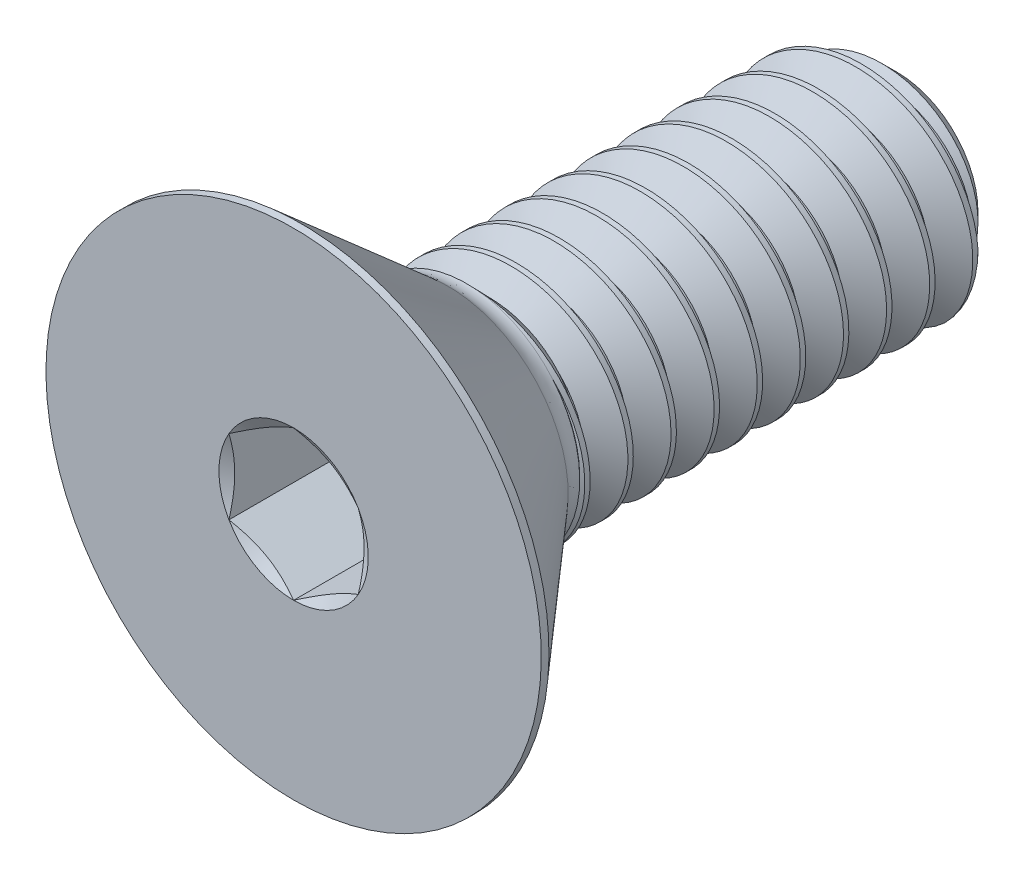
SolidWorks part; units mm, degrees
material "Alloy Steel"
ref_plane "Front" through (0, 0, 0) normal (0, 0, 1) x (1, 0, 0)
ref_plane "Top" through (0, 0, 0) normal (0, 1, 0) x (1, 0, 0)
ref_plane "Right" through (0, 0, 0) normal (1, 0, 0) x (0, 0, -1)
sketch "Sketch1" plane through (0, 0, 0) normal (1, 0, 0) x (0, 0, -1)
  line L0 (0, 4.5593) -> (0.1422, 4.5593) construction
  line L1 (0.1422, 4.5593) -> (2.8448, 2.21) construction
  line L2 (0, 2.0828) -> (11.1125, 2.0828)
  line L3 (11.1125, 2.0828) -> (11.1125, 0)
  line L4 (11.1125, 0) -> (0, 0)
  line L5 (0, 0) -> (0, 4.5593) construction
  line L6 (0, 4.5593) -> (0, -4.5593) construction
  line L7 (11.1125, 2.0828) -> (11.1125, -2.0828) construction
  line L8 (0, -4.5593) -> (0.1422, -4.5593) construction
  line L9 (0.1422, -4.5593) -> (2.8448, -2.21) construction
  line L11 (0, 2.0828) -> (0, 0)
  line L12 (3.185, 2.0828) -> (3.185, 0) construction
  line L13 (-14.2875, 0) -> (-14.2875, 2.0828) construction
  arc A1 (2.8448, 2.21) -> (3.185, 2.0828) centre (3.185, 2.6014) ccw construction
  dimension "D1" = 0.1422
  dimension "Head Ht" = 2.8448
  dimension "Head Dia" = 9.1186
  dimension "Dia" = 4.1656
  dimension "Lg" = 11.1125
  dimension "Head Angle" = 82
  dimension "Min Thread" = 25.4
revolve "Revolve1" add sketch "Sketch1" angle 360 mid plane about L4
sketch "Sketch3" plane through (0, 0, -11.1125) normal (0, 0, -1) x (-1, 0, 0)
  circle A0 centre (0, 0) radius 2.0828
curve "Helix/Spiral1" pitch 0.7937 height 11.1125 radius 2.0828 centre (0, 0, -11.1125) axis (0, 0, 1) start towards (0, 1, 0)
sketch "Sketch2" plane through (0, 0, 0) normal (1, 0, 0) x (0, 0, -1)
  line L0 (11.1125, 2.0828) -> (11.807, 2.0828)
  line L1 (11.807, 2.0828) -> (11.5094, 1.5672)
  line L2 (11.5094, 1.5672) -> (11.4102, 1.5672)
  line L3 (11.4102, 1.5672) -> (11.1125, 2.0828)
  line L4 (11.2613, 1.825) -> (11.6582, 1.825) construction
  dimension "D1" = 60
  dimension "D2" = 0.0992
  dimension "D3" = 0.3969
ref_plane "Plane2" through (0, 0, 14.2875) normal (0, 0, 1) x (1, 0, 0)
chamfer "Chamfer1" distance 0.5953 angle 45 1 edges at (-2.0828, 0, -11.1125)
sweep "Cut-Sweep1" cut profiles "Sketch2" path "Helix/Spiral1"
sketch "Sketch7" plane through (0, 0, 0) normal (1, 0, 0) x (0, 0, -1)
  line L0 (0, 4.5593) -> (0.1422, 4.5593) construction
  line L1 (0.1422, 4.5593) -> (2.8448, 2.21) construction
  line L2 (0, 4.5593) -> (0.1422, 4.5593)
  line L3 (0.1422, 4.5593) -> (2.8448, 2.21)
  line L4 (3.185, 2.0828) -> (3.185, 0) construction
  line L5 (3.185, 2.0828) -> (3.185, 0)
  line L7 (0, 0) -> (0, 4.5593) construction
  line L8 (0, 0) -> (0, 4.5593)
  line L9 (0, 0) -> (3.185, 0)
  line L10 (5.7417, 0) -> (-5.7417, 0) construction
  arc A0 (2.8448, 2.21) -> (3.185, 2.0828) centre (3.185, 2.6014) ccw construction
  arc A1 (2.8448, 2.21) -> (3.185, 2.0828) centre (3.185, 2.6014) ccw
revolve "Revolve2" add sketch "Sketch7" angle 360 mid plane about L9
ref_plane "Plane1" through (0, 0, -3.185) normal (0, 0, 1) x (1, 0, 0)
sketch "Sketch8" plane through (0, 0, -3.185) normal (0, 0, 1) x (1, 0, 0)
  circle A0 centre (0, 0) radius 2.0828
extrude "Boss-Extrude1" add sketch "Sketch8" against normal through all draft 46
sketch "Sketch5" plane through (0, 0, 0) normal (0, 0, 1) x (1, 0, 0)
  line L0 (0, 0) -> (-1.3748, 0) construction
  line L1 (0, 0) -> (-2.7496, 1.5875) construction
  line L2 (0, 0) -> (-2.7496, -1.5875) construction
  line L6 (0, 1.3748) -> (0, 1.1339) construction
  line L7 (0, 1.1339) -> (0, 0.893) construction
  line L9 (0, 1.3748) -> (-1.1906, 0.6874)
  line L10 (-1.1906, 0.6874) -> (-1.1906, -0.6874)
  line L11 (-1.1906, -0.6874) -> (0, -1.3748)
  line L12 (0, -1.3748) -> (1.1906, -0.6874)
  line L13 (1.1906, -0.6874) -> (1.1906, 0.6874)
  line L14 (1.1906, 0.6874) -> (0, 1.3748)
  circle A0 centre (0, 0) radius 1.3748 construction
  circle A1 centre (0, 0) radius 1.1339 construction
  circle A2 centre (0, 0) radius 0.893 construction
  circle A3 centre (0, 0) radius 1.1906 construction
  dimension "D3" = 1.7859
  dimension "Hex" = 2.3813
  dimension "D4" = 30
  dimension "D5" = 30
extrude "Cut-Extrude2" cut sketch "Sketch5" against normal blind 1.9914
sketch "Sketch6" plane through (0, 0, 0) normal (0, 0, 1) x (1, 0, 0)
  circle A0 centre (0, 0) radius 1.3748
extrude "Cut-Extrude3" cut sketch "Sketch6" against normal blind 1.9914 draft 60
sketch "Sketch9" [suppressed] plane through (0, 0, -3.6076) normal (0, 0, 1) x (1, 0, 0)
  circle A1 centre (0, 0) radius 2.413
  circle A2 centre (0, 0) radius 2.413
  point P0 (0, 2.413)
  dimension "D1" = 0
extrude "Boss-Extrude2" [suppressed] add sketch "Sketch9" against normal up to surface (15.4424 mm away) up to plane "Plane2"
sketch "Sketch10" plane through (0, 0, 0) normal (1, 0, 0) x (0, 0, -1)
  line L0 (11.1125, 2.0828) -> (11.1125, -2.0828) construction
  point P0 (9.9219, -2.0828)
  dimension "D1" = 1.1906
equation "\"D3@Helix/Spiral1\" = \"Lg@Sketch1\""
equation "\"D2@Sketch2\" = \"D4@Helix/Spiral1\" * .125"
equation "\"D3@Sketch2\" = \"D4@Helix/Spiral1\" * .5"
equation "\"D1@Chamfer1\" = \"D4@Helix/Spiral1\" * .75"
equation "\"D1@Cut-Extrude2\" = \"Head Ht@Sketch1\" * .7"
equation "\"D1@Sketch1\" = \"Head Ht@Sketch1\" * .05"
equation "\"D1@Sketch10\" = \"D4@Helix/Spiral1\" * 1.5"
equation "\"D1@Cut-Extrude3\" = \"D1@Cut-Extrude2\""
equation "\"D3@Sketch5\" = \"Hex@Sketch5\" * .75"
